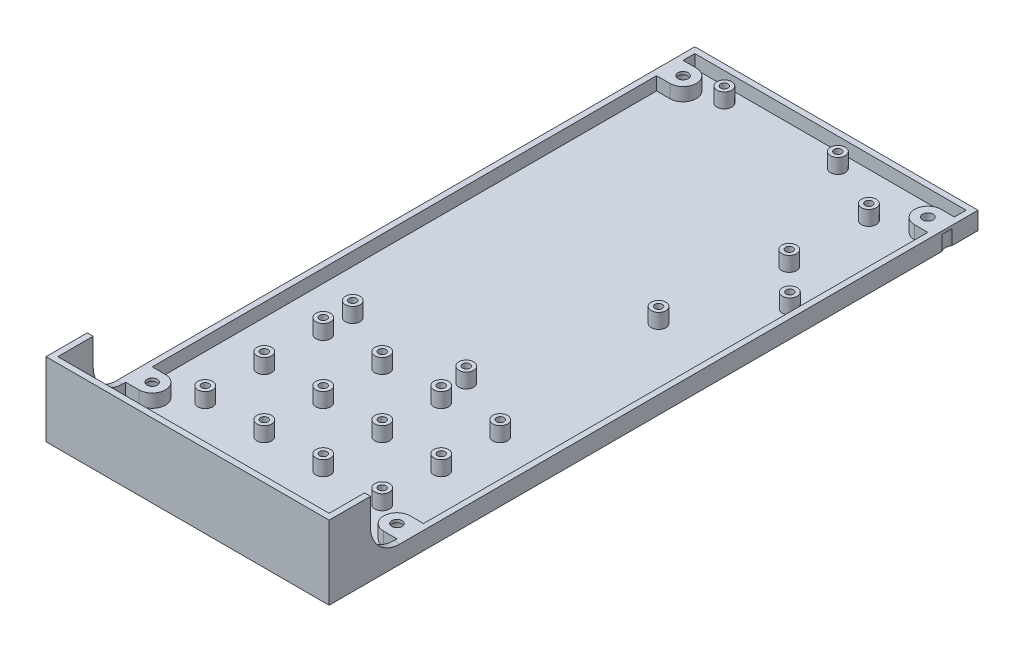
SolidWorks part; units mm, degrees
ref_plane "Front Plane" through (0, 0, 0) normal (0, 0, 1) x (1, 0, 0)
ref_plane "Top Plane" through (0, 0, 0) normal (0, 1, 0) x (1, 0, 0)
ref_plane "Right Plane" through (0, 0, 0) normal (1, 0, 0) x (0, 0, -1)
sketch "Sketch1" plane through (0, 0, 0) normal (0, 1, 0) x (1, 0, 0)
  line L1 (0, 5.4678) -> (96, 5.4678)
  line L2 (0, 5.4678) -> (0, 225.4678)
  line L3 (0, 225.4678) -> (96, 225.4678)
  line L4 (96, 5.4678) -> (96, 225.4678)
  dimension "D1" = 220
  dimension "D2" = 96
extrude "Boss-Extrude1" add sketch "Sketch1" along normal blind 25
sketch "Sketch2" plane through (0, 25, 0) normal (0, 1, 0) x (1, 0, 0)
  line L0 (2, 223.4678) -> (2, 219.4678)
  line L1 (2, 7.4678) -> (94, 7.4678)
  line L2 (94, 7.4678) -> (94, 30.4678)
  line L3 (94, 223.4678) -> (2, 223.4678)
  line L4 (0, 225.4678) -> (0, 5.4678)
  line L5 (0, 5.4678) -> (96, 5.4678)
  line L6 (96, 5.4678) -> (96, 225.4678)
  line L7 (96, 225.4678) -> (0, 225.4678)
  line L8 (0, 225.4678) -> (0, 5.4678)
  line L9 (0, 5.4678) -> (96, 5.4678)
  line L10 (96, 5.4678) -> (96, 225.4678)
  line L11 (96, 225.4678) -> (0, 225.4678)
  line L12 (94, 39.4678) -> (89.5, 39.4678)
  line L13 (89.5, 210.4678) -> (94, 210.4678)
  line L14 (89.5, 219.4678) -> (94, 219.4678)
  line L15 (6.5, 219.4678) -> (2, 219.4678)
  line L16 (6.5, 210.4678) -> (2, 210.4678)
  line L17 (6.5, 30.4678) -> (2, 30.4678)
  line L18 (6.5, 39.4678) -> (2, 39.4678)
  line L19 (2, 30.4678) -> (2, 7.4678)
  line L20 (89.5, 30.4678) -> (94, 30.4678)
  line L21 (2, 223.4678) -> (2, 7.4678) construction
  line L22 (94, 39.4678) -> (94, 210.4678)
  line L23 (94, 219.4678) -> (94, 223.4678)
  line L24 (94, 7.4678) -> (94, 223.4678) construction
  line L25 (2, 210.4678) -> (2, 39.4678)
  arc A0 (6.5, 210.4678) -> (6.5, 219.4678) centre (6.5, 214.9678) ccw
  arc A1 (89.5, 219.4678) -> (89.5, 210.4678) centre (89.5, 214.9678) ccw
  arc A2 (6.5, 30.4678) -> (6.5, 39.4678) centre (6.5, 34.9678) ccw
  arc A3 (89.5, 39.4678) -> (89.5, 30.4678) centre (89.5, 34.9678) ccw
  dimension "D3" = 9
  dimension "D4" = 6.5
  dimension "D5" = 6.5
  dimension "D7" = 180
  dimension "D6" = 10.5
  dimension "D1" = 0
  dimension "D2" = 2
extrude "Cut-Extrude1" cut sketch "Sketch2" against normal blind 23.5 contours L12 A3 L20 L2 L1 L19 L17 A2 L18 L25 L16 A0 L15 L0 L3 L23 L14 A1 L13 L22
sketch "Sketch3" plane through (96, 0, 0) normal (1, 0, 0) x (0, 0, -1)
  line L0 (225.4678, 6) -> (29.4678, 6)
  line L1 (225.4678, 25) -> (225.4678, 0) construction
  line L3 (19.4678, 25) -> (19.4678, 16)
  line L4 (5.4678, 25) -> (225.4678, 25) construction
  line L5 (19.4678, 25) -> (225.4678, 25)
  line L6 (225.4678, 25) -> (225.4678, 6)
  line L7 (5.4678, 0) -> (225.4678, 0) construction
  line L8 (5.4678, 25) -> (5.4678, 0) construction
  arc A0 (29.4678, 6) -> (19.4678, 16) centre (29.4678, 16) cw
  dimension "D1" = 10
  dimension "D2" = 6
  dimension "D3" = 14
extrude "Cut-Extrude2" cut sketch "Sketch3" against normal up to surface (96 mm away) up to face at (0, 12.5, -115.4678)
sketch "Sketch4" plane through (0, 6, 0) normal (0, 1, 0) x (1, 0, 0)
  circle A0 centre (6.5, 34.9678) radius 1.75
  circle A1 centre (89.5, 34.9678) radius 1.75
  circle A2 centre (89.5, 214.9678) radius 1.75
  circle A3 centre (6.5, 214.9678) radius 1.75
  dimension "D1" = 3.5
extrude "Cut-Extrude3" cut sketch "Sketch4" against normal up to next
sketch "Sketch5" plane through (0, 0, 0) normal (0, -1, 0) x (1, 0, 0)
  circle A0 centre (6.5, -34.9678) radius 3
  circle A1 centre (89.5, -34.9678) radius 3
  circle A2 centre (6.5, -214.9678) radius 3
  circle A3 centre (98.5, -214.9678) radius 3
  dimension "D1" = 6
extrude "Cut-Extrude4" cut sketch "Sketch5" against normal blind 5
sketch "Croquis2" plane through (0, 1.5, 0) normal (0, 1, 0) x (1, 0, 0)
  line L0 (12, 223.4678) -> (12, 87.4678) construction
  line L1 (60.5, 223.4678) -> (12, 223.4678) construction
  line L2 (60.5, 87.4678) -> (60.5, 223.4678) construction
  line L3 (12, 87.4678) -> (60.5, 87.4678) construction
  line L4 (84, 203.4678) -> (68, 203.4678) construction
  line L5 (68, 186.4678) -> (84, 186.4678) construction
  circle A0 centre (76, 208.4678) radius 2.5
  circle A1 centre (76, 181.4678) radius 2.5
  circle A2 centre (70.6, 142.5678) radius 2.5
  circle A3 centre (88.6, 169.0678) radius 2.5
  circle A4 centre (17, 92.4678) radius 2.5
  circle A5 centre (55.5, 92.4678) radius 2.5
  circle A6 centre (55.5, 218.4678) radius 2.5
  circle A7 centre (17, 218.4678) radius 2.5
  circle A8 centre (17, 218.4678) radius 1.25
  circle A9 centre (55.5, 218.4678) radius 1.25
  circle A10 centre (76, 208.4678) radius 1.25
  circle A11 centre (76, 181.4678) radius 1.25
  circle A12 centre (88.6, 169.0678) radius 1.25
  circle A13 centre (70.6, 142.5678) radius 1.25
  circle A14 centre (55.5, 92.4678) radius 1.25
  circle A15 centre (17, 92.4678) radius 1.25
  point P40 (76, 203.4678)
  dimension "D1" = 5
  dimension "D2" = 2.5
  dimension "D4" = 5
  dimension "D7" = 5
  dimension "D8" = 5
  dimension "D3" = 5
  dimension "D5" = 5
  dimension "D6" = 5
extrude "Saliente-Extruir1" add sketch "Croquis2" along normal blind 5
sketch "Croquis3" plane through (0, 1.5, 0) normal (0, 1, 0) x (1, 0, 0)
  line L0 (2, 7.4678) -> (94, 7.4678) construction
  line L1 (2, 30.4678) -> (2, 7.4678) construction
  circle A0 centre (17, 22.4678) radius 2.5
  circle A1 centre (17, 22.4678) radius 1.25
  circle A2 centre (37, 22.4678) radius 2.5
  circle A3 centre (37, 22.4678) radius 1.25
  circle A4 centre (57, 22.4678) radius 2.5
  circle A5 centre (57, 22.4678) radius 1.25
  circle A6 centre (77, 22.4678) radius 2.5
  circle A7 centre (77, 22.4678) radius 1.25
  circle A8 centre (37, 42.4678) radius 2.5
  circle A9 centre (37, 42.4678) radius 1.25
  circle A10 centre (57, 42.4678) radius 2.5
  circle A11 centre (57, 42.4678) radius 1.25
  circle A12 centre (77, 42.4678) radius 2.5
  circle A13 centre (77, 42.4678) radius 1.25
  circle A14 centre (37, 62.4678) radius 2.5
  circle A15 centre (37, 62.4678) radius 1.25
  circle A16 centre (57, 62.4678) radius 2.5
  circle A17 centre (57, 62.4678) radius 1.25
  circle A18 centre (77, 62.4678) radius 2.5
  circle A19 centre (77, 62.4678) radius 1.25
  circle A20 centre (37, 82.4678) radius 2.5
  circle A21 centre (37, 82.4678) radius 1.25
  circle A22 centre (57, 82.4678) radius 2.5
  circle A23 centre (57, 82.4678) radius 1.25
  circle A24 centre (77, 82.4678) radius 2.5
  circle A25 centre (77, 82.4678) radius 1.25
  circle A26 centre (17, 42.4678) radius 2.5
  circle A27 centre (17, 42.4678) radius 1.25
  circle A28 centre (17, 62.4678) radius 2.5
  circle A29 centre (17, 62.4678) radius 1.25
  circle A30 centre (17, 82.4678) radius 2.5
  circle A31 centre (17, 82.4678) radius 1.25
  dimension "D1" = 5
  dimension "D2" = 2.5
  dimension "D3" = 15
  dimension "D4" = 15
  dimension "D5" = 4
  dimension "D6" = 4
extrude "Saliente-Extruir2" add sketch "Croquis3" along normal blind 5
